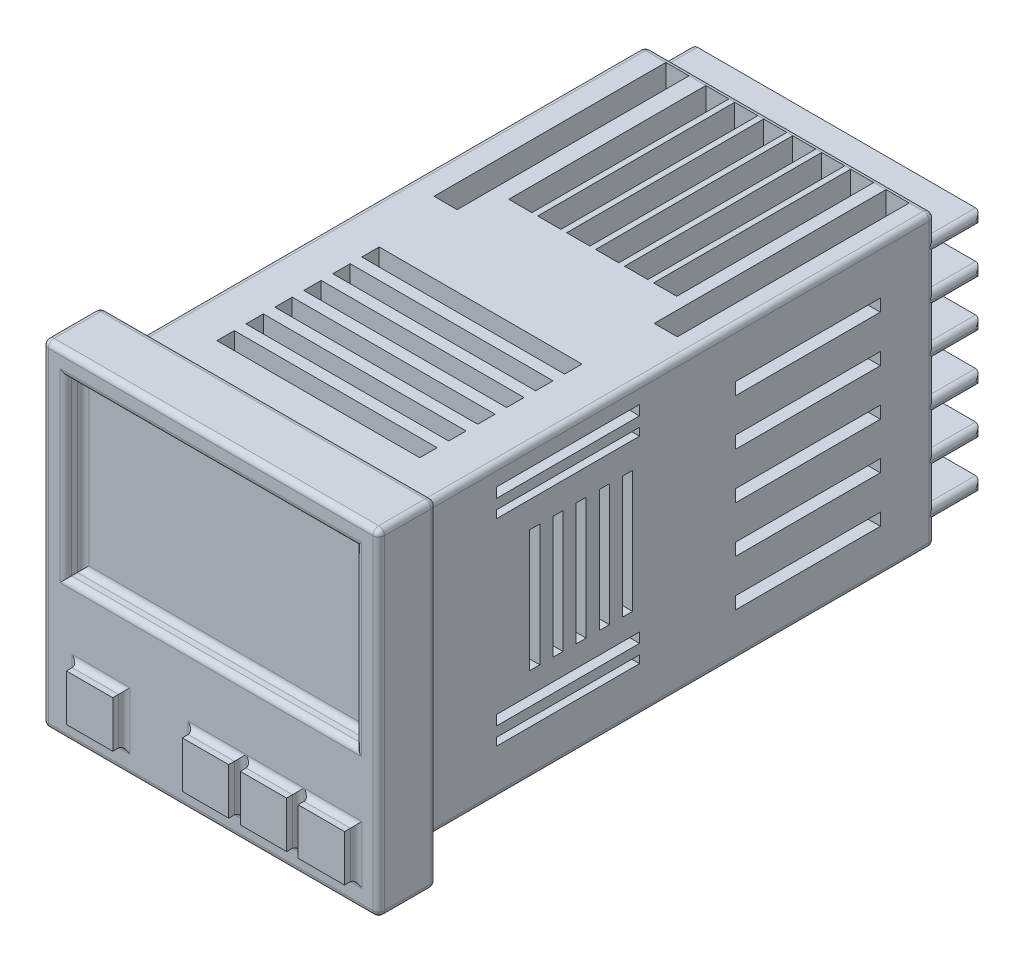
SolidWorks part; units mm, degrees
ref_plane "Plano frontal" through (0, 0, 0) normal (0, 0, 1) x (1, 0, 0)
ref_plane "Plano superior" through (0, 0, 0) normal (0, 1, 0) x (1, 0, 0)
ref_plane "Plano direito" through (0, 0, 0) normal (1, 0, 0) x (0, 0, -1)
sketch "Esboço1" plane through (0, 0, 0) normal (0, 0, 1) x (1, 0, 0)
  line L1 (25, -25) -> (-25, -25)
  line L2 (25, -25) -> (25, 25)
  line L3 (25, 25) -> (-25, 25)
  line L4 (-25, -25) -> (-25, 25)
  line L5 (25, -25) -> (-25, 25) construction
  line L6 (25, 25) -> (-25, -25) construction
  point P0 (0, 0)
  dimension "D1" = 50
  dimension "D2" = 50
extrude "Ressalto-extrusão1" add sketch "Esboço1" along normal blind 100
sketch "Esboço2" plane through (0, 0, 100) normal (0, 0, 1) x (1, 0, 0)
  line L0 (29, 29) -> (-29, 29)
  line L1 (-29, 29) -> (-29, -29)
  line L2 (-29, -29) -> (29, -29)
  line L3 (29, -29) -> (29, 29)
  line L4 (-25, 25) -> (-25, -25)
  line L5 (-25, -25) -> (25, -25)
  line L6 (25, -25) -> (25, 25)
  line L7 (25, 25) -> (-25, 25)
  line L8 (-25, 25) -> (-25, -25)
  line L9 (-25, -25) -> (25, -25)
  line L10 (25, -25) -> (25, 25)
  line L11 (25, 25) -> (-25, 25)
  dimension "D1" = 0
  dimension "D2" = 4
extrude "Ressalto-extrusão2" add sketch "Esboço2" against normal blind 10
sketch "Esboço3" plane through (0, 0, 100) normal (0, 0, 1) x (1, 0, 0)
  line L0 (29, 29) -> (-29, 29) construction
  line L1 (25, -5) -> (-25, -5)
  line L2 (25, -5) -> (25, 25)
  line L3 (25, 25) -> (-25, 25)
  line L4 (-25, -5) -> (-25, 25)
  line L5 (25, -5) -> (-25, 25) construction
  line L6 (25, 25) -> (-25, -5) construction
  line L7 (-29, 29) -> (-29, -29) construction
  line L8 (29, -29) -> (29, 29) construction
  point P0 (0, 10)
  dimension "D1" = 4
  dimension "D2" = 4
  dimension "D3" = 4
  dimension "D4" = 30
extrude "Corte-extrusão1" cut sketch "Esboço3" against normal blind 3
sketch "Esboço4" plane through (0, 0, 100) normal (0, 0, 1) x (1, 0, 0)
  line L0 (-18.8915, -20.6526) -> (24.1129, -20.6526) construction
  line L1 (-22.8915, -16.6526) -> (-14.8915, -16.6526)
  line L2 (-22.8915, -16.6526) -> (-22.8915, -24.6526)
  line L3 (-22.8915, -24.6526) -> (-14.8915, -24.6526)
  line L4 (-14.8915, -16.6526) -> (-14.8915, -24.6526)
  line L5 (-22.8915, -16.6526) -> (-14.8915, -24.6526) construction
  line L6 (-22.8915, -24.6526) -> (-14.8915, -16.6526) construction
  line L8 (-2.8915, -24.6526) -> (5.1085, -24.6526)
  line L9 (-2.8915, -24.6526) -> (-2.8915, -16.6526)
  line L10 (-2.8915, -16.6526) -> (5.1085, -16.6526)
  line L11 (5.1085, -24.6526) -> (5.1085, -16.6526)
  line L12 (-2.8915, -24.6526) -> (5.1085, -16.6526) construction
  line L13 (-2.8915, -16.6526) -> (5.1085, -24.6526) construction
  line L14 (7.1085, -24.6526) -> (15.1085, -24.6526)
  line L15 (7.1085, -24.6526) -> (7.1085, -16.6526)
  line L16 (7.1085, -16.6526) -> (15.1085, -16.6526)
  line L17 (15.1085, -24.6526) -> (15.1085, -16.6526)
  line L18 (7.1085, -24.6526) -> (15.1085, -16.6526) construction
  line L19 (7.1085, -16.6526) -> (15.1085, -24.6526) construction
  line L20 (17.1085, -24.6526) -> (25.1085, -24.6526)
  line L21 (17.1085, -24.6526) -> (17.1085, -16.6526)
  line L22 (17.1085, -16.6526) -> (25.1085, -16.6526)
  line L23 (25.1085, -24.6526) -> (25.1085, -16.6526)
  line L24 (17.1085, -24.6526) -> (25.1085, -16.6526) construction
  line L25 (17.1085, -16.6526) -> (25.1085, -24.6526) construction
  point P0 (-18.8915, -20.6526)
  point P7 (1.1085, -20.6526)
  point P12 (11.1085, -20.6526)
  point P17 (21.1085, -20.6526)
  dimension "D1" = 8
  dimension "D2" = 8
  dimension "D3" = 10
  dimension "D4" = 10
  dimension "D5" = 20
extrude "Ressalto-extrusão3" add sketch "Esboço4" along normal blind 2
sketch "Esboço5" plane through (25, 0, 0) normal (1, 0, 0) x (0, 0, -1)
  line L0 (0, 21) -> (8, 21)
  line L1 (0, -25) -> (0, 25) construction
  line L2 (8, 21) -> (8, 19)
  line L3 (8, 19) -> (0, 19)
  line L4 (0, 19) -> (0, 21)
  line L5 (-90, 25) -> (0, 25) construction
  line L6 (8, 11) -> (0, 11)
  line L7 (0, 13) -> (8, 13)
  line L8 (8, 13) -> (8, 11)
  line L9 (0, 11) -> (0, 13)
  line L10 (8, 3) -> (0, 3)
  line L11 (0, 5) -> (8, 5)
  line L12 (8, 5) -> (8, 3)
  line L13 (0, 3) -> (0, 5)
  line L14 (8, -5) -> (0, -5)
  line L15 (0, -3) -> (8, -3)
  line L16 (8, -3) -> (8, -5)
  line L17 (0, -5) -> (0, -3)
  line L18 (8, -13) -> (0, -13)
  line L19 (0, -11) -> (8, -11)
  line L20 (8, -11) -> (8, -13)
  line L21 (0, -13) -> (0, -11)
  line L22 (8, -21) -> (0, -21)
  line L23 (0, -19) -> (8, -19)
  line L24 (8, -19) -> (8, -21)
  line L25 (0, -21) -> (0, -19)
  dimension "D1" = 8
  dimension "D2" = 2
  dimension "D3" = 4
  dimension "D4" = 6
extrude "Ressalto-extrusão4" add sketch "Esboço5" against normal up to surface (50 mm away) up to face at (-25, 0, 45)
fillet "Filete1" radius 1 96 edges at (0, -25, 0) (0, -25, 90) (-25, -25, 45) (-25, -21, -4) (-25, -20, -8) (-25, -19, -4) (-25, -13, -4) (-25, -12, -8) (-25, -11, -4) (-25, -5, -4) (-25, -4, -8) (-25, -3, -4) (-25, 3, -4) (-25, 4, -8) (-25, 5, -4) (-25, 11, -4) (-25, 12, -8) (-25, 13, -4) (-25, 20, -8) (-25, 0, 90) (25, 20, -8) (25, 13, -4) (25, 12, -8) (25, 11, -4) (25, 5, -4) (25, 4, -8) (25, 3, -4) (25, -3, -4) (25, -4, -8) (25, -5, -4) (25, -11, -4) (25, -12, -8) (25, -13, -4) (25, -19, -4) (25, -20, -8) (25, -21, -4) (25, -25, 45) (25, 0, 90) (-25, 25, 45) (0, 25, 0) (25, 25, 45) (0, 25, 90) (0, 29, 90) (29, 29, 95) (29, 0, 90) (-29, 0, 90) (-29, 29, 95) (29, -29, 95) (0, -29, 90) (-29, -29, 95) (0, 25, 97) (25, 10, 97) (0, -5, 97) (-25, 10, 97) (17.1085, -20.6526, 100) (21.1085, -24.6526, 100) (25.1085, -20.6526, 100) (21.1085, -16.6526, 100) (-2.8915, -20.6526, 100) (1.1085, -24.6526, 100) (5.1085, -20.6526, 100) (1.1085, -16.6526, 100) (0, -29, 100) (-29, 0, 100) (0, 29, 100) (29, 0, 100) (0, -5, 100) (25, 10, 100) (0, 25, 100) (-25, 10, 100) (-22.8915, -20.6526, 100) (-18.8915, -24.6526, 100) (-14.8915, -20.6526, 100) (-18.8915, -16.6526, 100) (7.1085, -20.6526, 100) (11.1085, -24.6526, 100) (15.1085, -20.6526, 100) (11.1085, -16.6526, 100)
sketch "Esboço6" plane through (0, 0, 90) normal (0, 0, -1) x (-1, 0, 0)
  line L1 (-67.5, -92.5) -> (67.5, -92.5)
  line L2 (-67.5, -92.5) -> (-67.5, 92.5)
  line L3 (-67.5, 92.5) -> (67.5, 92.5)
  line L4 (67.5, -92.5) -> (67.5, 92.5)
  line L5 (-67.5, -92.5) -> (67.5, 92.5) construction
  line L6 (-67.5, 92.5) -> (67.5, -92.5) construction
  point P0 (0, 0)
  dimension "D1" = 135
  dimension "D2" = 185
extrude "Ressalto-extrusão5" [suppressed] add sketch "Esboço6" along normal blind 3
sketch "Sketch1" plane through (25, 0, 0) normal (1, 0, 0) x (0, 0, -1)
  line L1 (-34.4391, 16.7479) -> (-9.4391, 16.7479)
  line L2 (-34.4391, 16.7479) -> (-34.4391, 14.6303)
  line L3 (-34.4391, 14.6303) -> (-9.4391, 14.6303)
  line L4 (-9.4391, 16.7479) -> (-9.4391, 14.6303)
  dimension "D1" = 25
extrude "Cut-Extrude1" cut sketch "Sketch1" against normal blind 10
sketch "Sketch2" plane through (25, 0, 0) normal (1, 0, 0) x (0, 0, -1)
  line L0 (-9.4391, 14.6303) -> (-9.4391, -24) construction
  line L1 (-89, -24) -> (-1, -24) construction
pattern_linear "LPattern1" count 5 spacing 8 along (0, -1, 0) of "Cut-Extrude1"
sketch "Sketch3" plane through (25, 0, 0) normal (1, 0, 0) x (0, 0, -1)
  line L1 (-69.9373, 12.3646) -> (-68.1986, 12.3646)
  line L2 (-69.9373, 12.3646) -> (-69.9373, -8.6939)
  line L3 (-69.9373, -8.6939) -> (-68.1986, -8.6939)
  line L4 (-68.1986, 12.3646) -> (-68.1986, -8.6939)
extrude "Cut-Extrude2" cut sketch "Sketch3" against normal blind 10
sketch "Sketch4" plane through (25, 0, 0) normal (1, 0, 0) x (0, 0, -1)
  line L0 (-68.1986, 12.3646) -> (-48.7521, 12.3646) construction
pattern_linear "LPattern2" count 5 spacing 4 along (0, 0, -1) of "Cut-Extrude2"
sketch "Sketch5" plane through (25, 0, 0) normal (1, 0, 0) x (0, 0, -1)
  line L1 (-75.6482, 21.6188) -> (-50.9952, 21.6188)
  line L2 (-75.6482, 21.6188) -> (-75.6482, 19.9121)
  line L3 (-75.6482, 19.9121) -> (-50.9952, 19.9121)
  line L4 (-50.9952, 21.6188) -> (-50.9952, 19.9121)
  line L5 (-75.6482, 18.2053) -> (-50.9952, 18.2053)
  line L6 (-75.6482, 18.2053) -> (-75.6482, 16.8778)
  line L7 (-75.6482, 16.8778) -> (-50.9952, 16.8778)
  line L8 (-50.9952, 18.2053) -> (-50.9952, 16.8778)
extrude "Cut-Extrude3" cut sketch "Sketch5" against normal blind 5
sketch "Sketch6" plane through (25, 0, 0) normal (1, 0, 0) x (0, 0, -1)
  line L1 (-89, -24) -> (-1, -24) construction
  line L2 (-50.9952, 16.8778) -> (-50.9952, -24) construction
pattern_linear "LPattern3" count 2 spacing 34 along (0, -1, 0) of "Cut-Extrude3"
sketch "Sketch7" plane through (0, 25, 0) normal (0, 1, 0) x (1, 0, 0)
  line L0 (24, -1) -> (-24, -1) construction
  line L1 (-20.4587, -1) -> (-16.4587, -1)
  line L2 (-20.4587, -1) -> (-20.4587, -41)
  line L3 (-20.4587, -41) -> (-16.4587, -41)
  line L4 (-16.4587, -1) -> (-16.4587, -41)
  dimension "D1" = 4
  dimension "D2" = 40
extrude "Cut-Extrude4" cut sketch "Sketch7" against normal blind 5
sketch "Sketch8" plane through (0, 25, 0) normal (0, 1, 0) x (1, 0, 0)
  line L0 (24, -1) -> (-16.4587, -1) construction
  line L1 (-13.5633, -1) -> (-9.5633, -1)
  line L2 (-13.5633, -1) -> (-13.5633, -35)
  line L3 (-13.5633, -35) -> (-9.5633, -35)
  line L4 (-9.5633, -1) -> (-9.5633, -35)
  dimension "D1" = 4
  dimension "D2" = 34
extrude "Cut-Extrude5" cut sketch "Sketch8" against normal blind 5
sketch "Sketch9" plane through (0, 25, 0) normal (0, 1, 0) x (1, 0, 0)
  line L0 (-9.5633, -1) -> (41.9915, -1) construction
pattern_linear "LPattern4" count 6 spacing 5 along (1, 0, 0) of "Cut-Extrude5"
pattern_linear "LPattern5" count 2 spacing 38 along (1, 0, 0) of "Cut-Extrude4"
sketch "Sketch10" plane through (0, 25, 0) normal (0, 1, 0) x (1, 0, 0)
  line L1 (-17.6165, -53.3025) -> (17.3835, -53.3025)
  line L2 (-17.6165, -53.3025) -> (-17.6165, -56.3025)
  line L3 (-17.6165, -56.3025) -> (17.3835, -56.3025)
  line L4 (17.3835, -53.3025) -> (17.3835, -56.3025)
  dimension "D1" = 35
  dimension "D2" = 3
extrude "Cut-Extrude6" cut sketch "Sketch10" against normal blind 5
sketch "Sketch11" plane through (0, 25, 0) normal (0, 1, 0) x (1, 0, 0)
  line L0 (-17.6165, -53.3025) -> (-17.6165, -82.6531) construction
pattern_linear "LPattern6" count 6 spacing 5 along (0, 0, 1) of "Cut-Extrude6"
